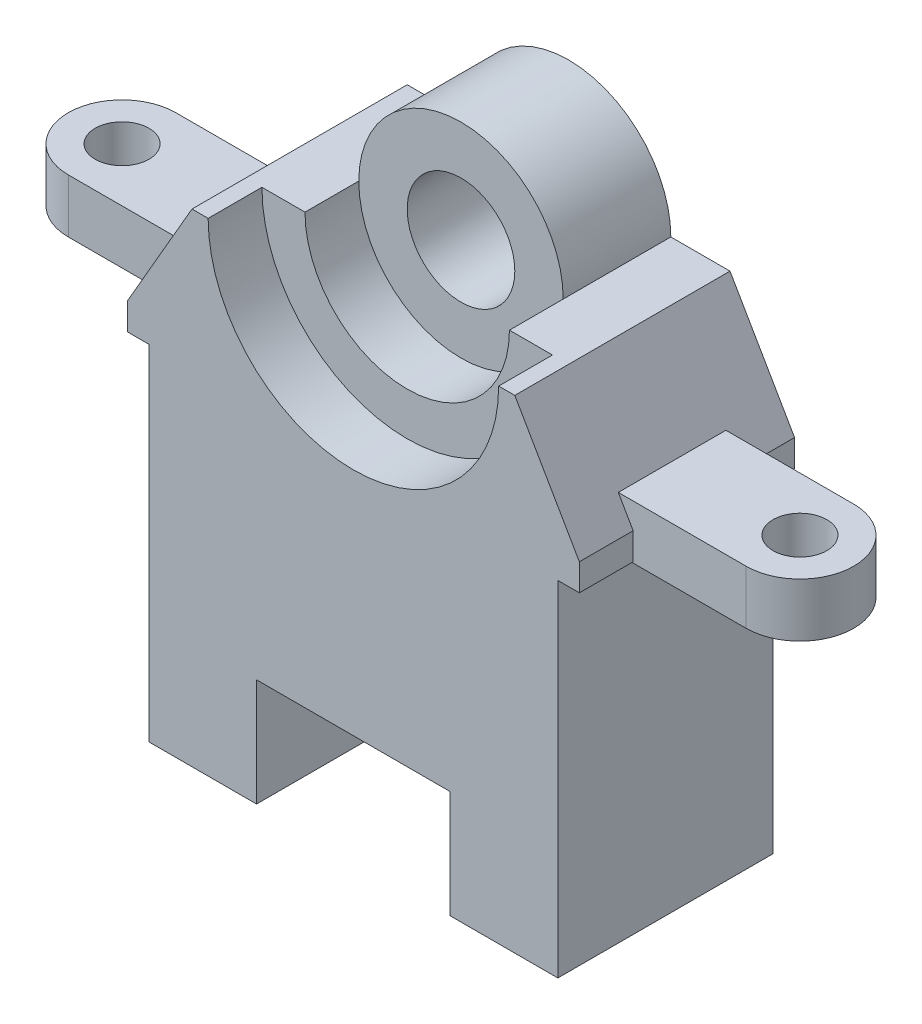
SolidWorks part; units mm, degrees
ref_plane "Front Plane" through (0, 0, 0) normal (0, 0, 1) x (1, 0, 0)
ref_plane "Top Plane" through (0, 0, 0) normal (0, 1, 0) x (1, 0, 0)
ref_plane "Right Plane" through (0, 0, 0) normal (1, 0, 0) x (0, 0, -1)
sketch "Sketch1" plane through (0, 0, 0) normal (0, 0, 1) x (1, 0, 0)
  line L1 (38, -89.7846) -> (38, -25.7846)
  line L2 (38, -25.7846) -> (42, -25.7846)
  line L3 (42, -25.7846) -> (42, -20.7846)
  line L4 (42, -20.7846) -> (30, 0)
  line L5 (0, 46.393) -> (0, -10.1774) construction
  line L6 (-42, -20.7846) -> (-30, 0)
  line L7 (-42, -25.7846) -> (-42, -20.7846)
  line L8 (-38, -25.7846) -> (-42, -25.7846)
  line L9 (-38, -89.7846) -> (-38, -25.7846)
  line L10 (-38, -89.7846) -> (38, -89.7846)
  line L12 (-30, 0) -> (30, 0)
  line L13 (0, 73.6174) -> (0, -60.2713) construction
  point P15 (0, 0)
  dimension "D1" = 76
  dimension "D2" = 64
  dimension "D3" = 60
  dimension "D4" = 5
  dimension "D5" = 4
  dimension "D6" = 60
extrude "Boss-Extrude1" add sketch "Sketch1" along normal mid plane 40
sketch "Sketch2" plane through (0, 0, 20) normal (0, 0, 1) x (1, 0, 0)
  line L0 (-38, -89.7846) -> (38, -89.7846) construction
  line L1 (-18, -89.7846) -> (18, -89.7846)
  line L2 (-18, -89.7846) -> (-18, -69.7846)
  line L3 (-18, -69.7846) -> (18, -69.7846)
  line L4 (18, -89.7846) -> (18, -69.7846)
  line L5 (0, 0) -> (0, -69.7846) construction
  dimension "D1" = 36
  dimension "D2" = 20
extrude "Cut-Extrude1" cut sketch "Sketch2" against normal through all
sketch "Sketch3" plane through (0, 0, 20) normal (0, 0, 1) x (1, 0, 0)
  line L0 (-27, 0) -> (27, 0)
  arc A0 (-27, 0) -> (27, 0) centre (0, 0) ccw
  dimension "D1" = 54
extrude "Cut-Extrude3" cut sketch "Sketch3" against normal blind 10 contours A0 L0
sketch "Sketch5" plane through (0, 0, 10) normal (0, 0, 1) x (1, 0, 0)
  line L0 (-19, 0) -> (19, 0)
  arc A0 (-19, 0) -> (19, 0) centre (0, 0) ccw
  dimension "D1" = 38
extrude "Cut-Extrude5" cut sketch "Sketch5" against normal blind 10 contours L0 A0
sketch "Sketch6" plane through (0, 0, 0) normal (0, 0, 1) x (1, 0, 0)
  circle A0 centre (0, 0) radius 19
  circle A1 centre (0, 0) radius 10
  line M1 (19, 0) -> (-19, 0)
  dimension "D1" = 20
  dimension "D2" = 38
extrude "Boss-Extrude2" add sketch "Sketch6" against normal up to surface (20 mm away) up to face at (0, -45.9582, -20)
extrude "Cut-Extrude6" cut sketch "Sketch6<2>" against normal through all contours A1 M1 | A1 M1 region at (0, 4.2441, 0) region at (0, -4.2441, 0)
sketch "Sketch6<2>" plane through (0, 0, 0) normal (0, 0, 1) x (1, 0, 0) same geometry as "Sketch6"
sketch "Sketch8" plane through (0, 0, 0) normal (0, 1, 0) x (1, 0, 0)
  line L0 (27, 10) -> (63, 10)
  line L1 (63, 0) -> (63, -10)
  line L2 (63, -10) -> (27, -10)
  line L3 (27, -10) -> (27, 10)
  line L4 (42, 0) -> (63, 0) construction
  line L5 (42, -20) -> (42, 20) construction
  arc A0 (63, -10) -> (63, 10) centre (63, 0) ccw
  dimension "D3" = 10
  dimension "D1" = 36
  dimension "D2" = 20
  dimension "D4" = 20
  dimension "D5" = 63
extrude "Boss-Extrude3" add sketch "Sketch8" along normal blind 10 from offset 26 contours A0 L0 L3 L2 region at (48.9838, 0, 0) offset against normal yes
mirror "Mirror1" about plane through (0, 0, 0) normal (1, 0, 0) of "Boss-Extrude3"
sketch "Sketch9" plane through (0, -16, 0) normal (0, 1, 0) x (1, 0, 0)
  circle A0 centre (-63, 0) radius 5
  dimension "D1" = 10
extrude "Cut-Extrude7" cut sketch "Sketch9" against normal through all
mirror "Mirror2" about plane through (0, 0, 0) normal (1, 0, 0) of "Cut-Extrude7"
